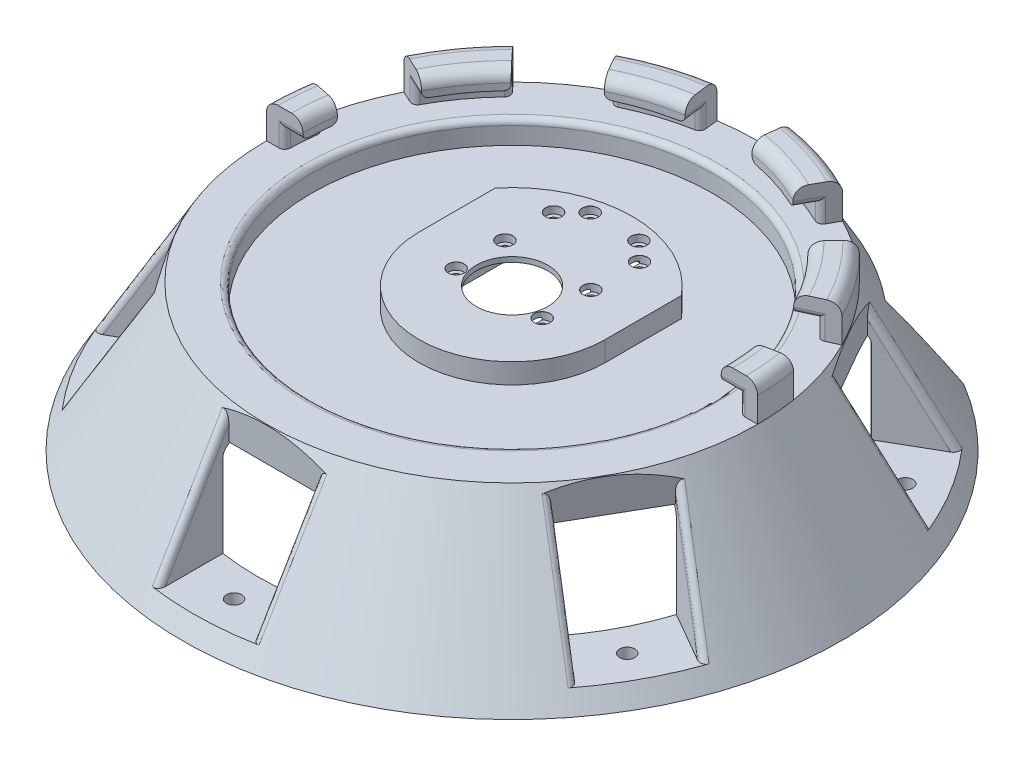
SolidWorks part; units mm, degrees
material "PLA"
ref_plane "Front Plane" through (0, 0, 0) normal (0, 0, 1) x (1, 0, 0)
ref_plane "Top Plane" through (0, 0, 0) normal (0, 1, 0) x (1, 0, 0)
ref_plane "Right Plane" through (0, 0, 0) normal (1, 0, 0) x (0, 0, -1)
sketch "Sketch1" plane through (0, 0, 0) normal (0, 0, 1) x (1, 0, 0)
  line L0 (0, 0) -> (-85.725, 0)
  line L1 (-85.725, 0) -> (-115.0544, -50.8)
  line L2 (-115.0544, -50.8) -> (0, -50.8)
  line L6 (0, 0) -> (0, -50.8) construction
  line L7 (0, 0) -> (0, -50.8)
  dimension "D1" = 85.725
  dimension "D3" = 50.8
  dimension "D4" = 60
revolve "Revolve1" add sketch "Sketch1" angle 360 about L6
sketch "Sketch2" plane through (0, 0, 0) normal (0, 1, 0) x (1, 0, 0)
  circle A0 centre (0, 0) radius 12.5
  dimension "D1" = 25
extrude "Cut-Extrude1" cut sketch "Sketch2" against normal through all
sketch "Sketch3" plane through (0, 0, 0) normal (0, 1, 0) x (1, 0, 0)
  line L0 (-32.5, 0) -> (-32.5, 26.6036)
  line L1 (-32.5, 26.6036) -> (32.5, 26.6036)
  line L2 (32.5, 26.6036) -> (32.5, 0)
  circle A0 centre (0, 0) radius 32.5
  circle A1 centre (0, 0) radius 70
  circle A2 centre (0, 0) radius 42
  circle M1 centre (0, 0) radius 12.5
  dimension "D1" = 65
  dimension "D2" = 140
  dimension "D3" = 84
extrude "Cut-Extrude2" cut sketch "Sketch3" against normal blind 8 contours A1 A0 L0 L1 L2 | A1 A2 region at (0, 0, 33.5845) region at (-68.0201, 0, 0)
sketch "Sketch7" plane through (0, -50.8, 0) normal (0, -1, 0) x (1, 0, 0)
  line L0 (3.6132, 88.8265) -> (-2.6643, -115.0235) construction
  line L1 (-88.0643, 0) -> (82.7357, 0) construction
  line L2 (-62.6643, -63.0586) -> (-62.6643, -115.0235)
  line L3 (-62.6643, -115.0235) -> (57.3357, -115.0235)
  line L4 (57.3357, -115.0235) -> (57.3357, -67.9399)
  arc A2 (57.3357, -67.9399) -> (-62.6643, -63.0586) centre (0, 0) ccw
  circle A3 centre (0, 0) radius 115.0544 construction
  dimension "D1" = 177.8
  dimension "D2" = 25.4
  dimension "D3" = 25.4
  dimension "D4" = 120
  dimension "D5" = 88.9
extrude "Cut-Extrude5" cut sketch "Sketch7" against normal blind 39 contours L3 L4 A2 L2
sketch "Sketch8" plane through (0, 0, 0) normal (0, 1, 0) x (1, 0, 0)
  line L0 (0, 0) -> (3.123, -115.012) construction
  line L2 (-13.0273, -123.925) -> (18.7227, -123.925)
  line L3 (-13.0273, -123.925) -> (-13.0273, -85.825)
  line L4 (-13.0273, -85.825) -> (18.7227, -85.825)
  line L5 (18.7227, -123.925) -> (18.7227, -85.825)
  line L6 (-13.0273, -123.925) -> (18.7227, -85.825) construction
  line L7 (-13.0273, -85.825) -> (18.7227, -123.925) construction
  arc A0 (-62.6643, 96.4919) -> (57.3357, 99.7504) centre (0, 0) ccw construction
  point P6 (2.8477, -104.875)
  dimension "D1" = 85.825
  dimension "D2" = 38.1
  dimension "D3" = 31.75
extrude "Cut-Extrude6" cut sketch "Sketch8" against normal blind 44.45
pattern_circular "CirPattern2" count 6 over 360 about axis through (0, 0, 0) along (0, 1, 0) of "Cut-Extrude6" reverse direction yes
sketch "Sketch9" plane through (0, 0, 0) normal (0, 1, 0) x (1, 0, 0)
  line L0 (0, 0) -> (3.123, -115.012) construction
  arc A0 (-62.6643, 96.4919) -> (57.3357, 99.7504) centre (0, 0) ccw construction
  circle A1 centre (2.7092, -99.772) radius 2.65
  dimension "D1" = 5.3
  dimension "D2" = 15.24
extrude "Cut-Extrude7" cut sketch "Sketch9" against normal through all
pattern_circular "CirPattern3" count 6 over 360 about axis through (0, 0, 0) along (0, 1, 0) of "Cut-Extrude7"
sketch "Sketch12" plane through (0, 0, 0) normal (0, 0, 1) x (1, 0, 0)
  line L0 (85.725, 0) -> (85.725, 12.7)
  line L1 (85.725, 12.7) -> (73.025, 12.7)
  line L2 (73.025, 12.7) -> (73.025, 6.35)
  line L3 (73.025, 6.35) -> (79.375, 6.35)
  line L4 (79.375, 6.35) -> (79.375, 0)
  line L5 (85.725, 0) -> (-85.725, 0) construction
  line L6 (0, 0) -> (0, 12.7) construction
  line L7 (12.5, 0) -> (-12.5, 0) construction
  line L8 (79.375, 0) -> (85.725, 0)
  point P13 (0, 6.35)
  point P14 (0, 0)
  dimension "D1" = 6.35
  dimension "D2" = 73.025
  dimension "D3" = 79.375
  dimension "D4" = 12.7
  dimension "D5" = 12.7
revolve "Revolve2" add sketch "Sketch12" angle 180 about L6
sketch "Sketch13" plane through (0, -11.8, 0) normal (0, -1, 0) x (1, 0, 0)
  line L0 (0, 13) -> (0, -34) construction
  line L1 (-13.0268, -34) -> (13.0268, -34)
  line L2 (-13.0268, -34) -> (-13.0268, 13)
  line L3 (-13.0268, 13) -> (13.0268, 13)
  line L4 (13.0268, -34) -> (13.0268, 13)
  line L5 (-13.0268, -34) -> (13.0268, 13) construction
  line L6 (-13.0268, 13) -> (13.0268, -34) construction
  point P0 (0, -10.5)
  dimension "D1" = 34
  dimension "D2" = 13
  dimension "D3" = 0
  dimension "D4" = 26.0535
extrude "Cut-Extrude8" cut sketch "Sketch13" against normal offset from surface (9.05 mm away) 2.75 up to face at (0, 0, -9.0259)
sketch "Sketch15" plane through (0, -11.8, 0) normal (0, -1, 0) x (1, 0, 0)
  line L0 (0, -1000) -> (0, 49000) construction
  point P1 (-15, 4.5)
  point P4 (-15, -12.5)
  point P5 (-15, -29.5)
  point P6 (-8.5, -35.8)
  point P7 (8.5, -35.8)
  point P8 (15, -29.5)
  point P9 (15, -12.5)
  point P10 (15, 4.5)
  dimension "D1" = 17
  dimension "D2" = 17
  dimension "D3" = 4.5
  dimension "D4" = 15
  dimension "D5" = 8.5
  dimension "D6" = 35.8
sketch "Sketch18" plane through (0, 12.7, 0) normal (0, 1, 0) x (1, 0, 0)
  line L0 (46.6433, 89.7185) -> (70.9138, 72.0849)
  line L1 (0, 201000) -> (0, -249000) construction
  line L2 (-15, 100) -> (-9, 50)
  line L3 (-9, 50) -> (9, 50)
  line L4 (9, 50) -> (15, 100)
  line L5 (-15, 100) -> (15, 100)
  line L6 (36.6704, 35.1608) -> (70.9138, 72.0849)
  line L7 (22.1081, 45.7409) -> (36.6704, 35.1608)
  line L8 (46.6433, 89.7185) -> (22.1081, 45.7409)
  line L9 (90.4704, 45.1675) -> (99.7409, 16.6359)
  line L10 (50.334, 6.8913) -> (99.7409, 16.6359)
  line L11 (44.7717, 24.0104) -> (50.334, 6.8913)
  line L12 (90.4704, 45.1675) -> (44.7717, 24.0104)
  line L13 (99.7409, -16.6359) -> (90.4704, -45.1675)
  line L14 (44.7717, -24.0104) -> (90.4704, -45.1675)
  line L15 (50.334, -6.8913) -> (44.7717, -24.0104)
  line L16 (99.7409, -16.6359) -> (50.334, -6.8913)
  line L17 (70.9138, -72.0849) -> (46.6433, -89.7185)
  line L18 (22.1081, -45.7409) -> (46.6433, -89.7185)
  line L19 (36.6704, -35.1608) -> (22.1081, -45.7409)
  line L20 (70.9138, -72.0849) -> (36.6704, -35.1608)
  line L21 (15, -100) -> (-15, -100)
  line L22 (-9, -50) -> (-15, -100)
  line L23 (9, -50) -> (-9, -50)
  line L24 (15, -100) -> (9, -50)
  line L25 (-46.6433, -89.7185) -> (-70.9138, -72.0849)
  line L26 (-36.6704, -35.1608) -> (-70.9138, -72.0849)
  line L27 (-22.1081, -45.7409) -> (-36.6704, -35.1608)
  line L28 (-46.6433, -89.7185) -> (-22.1081, -45.7409)
  line L29 (-90.4704, -45.1675) -> (-99.7409, -16.6359)
  line L30 (-50.334, -6.8913) -> (-99.7409, -16.6359)
  line L31 (-44.7717, -24.0104) -> (-50.334, -6.8913)
  line L32 (-90.4704, -45.1675) -> (-44.7717, -24.0104)
  line L33 (-99.7409, 16.6359) -> (-90.4704, 45.1675)
  line L34 (-44.7717, 24.0104) -> (-90.4704, 45.1675)
  line L35 (-50.334, 6.8913) -> (-44.7717, 24.0104)
  line L36 (-99.7409, 16.6359) -> (-50.334, 6.8913)
  line L37 (-70.9138, 72.0849) -> (-46.6433, 89.7185)
  line L38 (-22.1081, 45.7409) -> (-46.6433, 89.7185)
  line L39 (-36.6704, 35.1608) -> (-22.1081, 45.7409)
  line L40 (-70.9138, 72.0849) -> (-36.6704, 35.1608)
  point P4 (0, 50)
  point P7 (0, 100)
  point P48 (0, 0)
  dimension "D1" = 18
  dimension "D2" = 50
  dimension "D3" = 30
  dimension "D4" = 50
  dimension "D5" = 10
extrude "Cut-Extrude9" cut sketch "Sketch18" against normal blind 12.7
sketch "Sketch20" plane through (0, -11.8, 0) normal (0, -1, 0) x (1, 0, 0)
  line L0 (-22.5, -33) -> (-12.5, -40)
  line L1 (22.5, 20) -> (-22.5, 20)
  line L2 (22.5, 20) -> (22.5, -40)
  line L3 (22.5, -40) -> (-22.5, -40)
  line L4 (-22.5, 20) -> (-22.5, -40)
  line L5 (22.5, 20) -> (-22.5, -40) construction
  line L6 (22.5, -40) -> (-22.5, 20) construction
  line L7 (-12.5, -40) -> (12.5, -40)
  line L8 (12.5, -40) -> (22.5, -33)
  point P0 (0, -10)
  line M11 (-13.0268, 13) -> (13.0268, 13)
  line M12 (13.0268, 13) -> (13.0268, -34)
  line M13 (13.0268, -34) -> (-13.0268, -34)
  line M14 (-13.0268, -34) -> (-13.0268, 13)
  dimension "D1" = 60
  dimension "D2" = 45
  dimension "D3" = 10
  dimension "D4" = 10
  dimension "D5" = 7
  dimension "D6" = 7
  dimension "D7" = 10
extrude "Cut-Extrude10" cut sketch "Sketch20" against normal offset from surface (6.3 mm away) 2.75 contours L3 L8 L2 L1 L4 L0 M14 M11 M12 M13 region at (-21.75, -11.8, -6.5) up to face at (0, -2.75, -10.5)
extrude "Cut-Extrude11" cut sketch "Sketch3<3>" against normal blind 1 contours A0 L1 M1 | A0 L1 L0 | L1 A0 | L1 A2 A0 | A0 L2 L1 | A0 region at (-28.056, 0, -14.587) region at (-28.5629, 0, -20.2686) region at (0, 0, -33.9353) region at (28.5629, 0, -20.2686) region at (0, 0, -28.9815)
sketch "Sketch3<3>" plane through (0, 0, 0) normal (0, 1, 0) x (1, 0, 0) same geometry as "Sketch3"
sketch "Sketch22" plane through (0, -1, 0) normal (0, 1, 0) x (1, 0, 0)
  circle A0 centre (-15, 12.5) radius 1.4
  circle A1 centre (-15, 29.5) radius 1.4
  circle A2 centre (-8.5, 35.8) radius 1.4
  circle A3 centre (8.5, 35.8) radius 1.4
  circle A4 centre (15, 29.5) radius 1.4
  circle A5 centre (15, 12.5) radius 1.4
  circle A6 centre (15, -4.5) radius 1.4
  circle A7 centre (-15, -4.5) radius 1.4
hole_wizard "CBORE for M2.5 SHCS1" positions "Sketch23" profile "Sketch24" counterbore size "M2.5" standard "ANSI Metric" end condition through all
sketch "Sketch23" plane through (0, -1, 0) normal (0, 1, 0) x (1, 0, 0)
  point P0 (-15, -4.5)
  point P3 (-15, 12.5)
  point P6 (-15, 29.5)
  point P9 (-8.5, 35.8)
  point P12 (8.5, 35.8)
  point P15 (15, 29.5)
  point P18 (15, 12.5)
  point P21 (15, -4.5)
sketch "Sketch24" plane through (-15, -1, 4.5) normal (1, 0, 0) x (0, 0, 1)
  line L0 (0, 0) -> (0, 49.8)
  line L1 (0, 49.8) -> (1.45, 49.8)
  line L3 (1.45, 49.8) -> (1.45, 2.5)
  line L4 (2.75, 2.5) -> (1.45, 2.5)
  line L5 (2.75, 2.5) -> (2.75, 0.025)
  line L6 (2.75, 0.025) -> (2.775, 0)
  line L7 (2.775, 0) -> (0, 0)
  line L8 (-2.75, 0.025) -> (-2.775, 0) construction
  line L11 (0, -6.35) -> (0, 107.95) construction
  dimension "Thru Hole Dia." = 2.9
  dimension "Thru Hole Depth" = 49.8
  dimension "C'Bore Dia." = 5.5
  dimension "C'Bore Depth" = 2.5
  dimension "Near C'Sink Dia." = 5.55
  dimension "Near C'Sink Angle" = 90
fillet "Fillet1" radius 4 12 edges at (85.4509, 12.7, -6.8497) (69.353, 12.7, -50.3879) (26.4905, 12.7, -81.5293) (-26.4905, 12.7, -81.5293) (-69.353, 12.7, -50.3879) (-85.4509, 12.7, -6.8497) (-72.8088, 12.7, -5.6148) (-59.0785, 12.7, -42.923) (-22.566, 12.7, -69.4509) (22.566, 12.7, -69.4509) (59.0785, 12.7, -42.923) (72.8088, 12.7, -5.6148)
fillet "Fillet2" radius 2 12 edges at (75.2789, 6.35, -11.8112) (76.2, 6.35, 0) (53.9595, 6.35, -53.8033) (67.8444, 6.35, -34.6924) (12.0293, 6.35, -75.2444) (34.4956, 6.35, -67.9447) (-12.0293, 6.35, -75.2444) (-34.4956, 6.35, -67.9447) (-53.9595, 6.35, -53.8033) (-67.8444, 6.35, -34.6924) (-75.2789, 6.35, -11.8112) (-76.2, 6.35, 0)
fillet "Fillet3" radius 2 12 edges at (-78.3963, 4.175, -12.4261) (-56.1201, 4.175, -56.1331) (-70.7278, 4.175, -36.0273) (-12.4079, 4.175, -78.3992) (56.1201, 4.175, -56.1331) (78.3963, 4.175, -12.4261) (-79.375, 4.175, 0) (-36.0437, 4.175, -70.7195) (12.4079, 4.175, -78.3992) (36.0437, 4.175, -70.7195) (70.7278, 4.175, -36.0273) (79.375, 4.175, 0)
fillet "Fillet4" radius 2 10 edges
fillet "Fillet5" radius 2 1 edges at (0, 0, 70)
fillet "Fillet6" radius 4 4 edges at (88.8529, -11.8, -2.8943) (-88.8529, -11.8, 2.8943) (-41.9199, -11.8, 78.396) (46.933, -11.8, 75.5017)
fillet "Fillet7" radius 4 1 edges at (61.7573, -11.8, -63.9472)
fillet "Fillet8" radius 4 1 edges at (-66.2697, -11.8, -59.2583)
fillet "Fillet9" radius 1 2 edges
